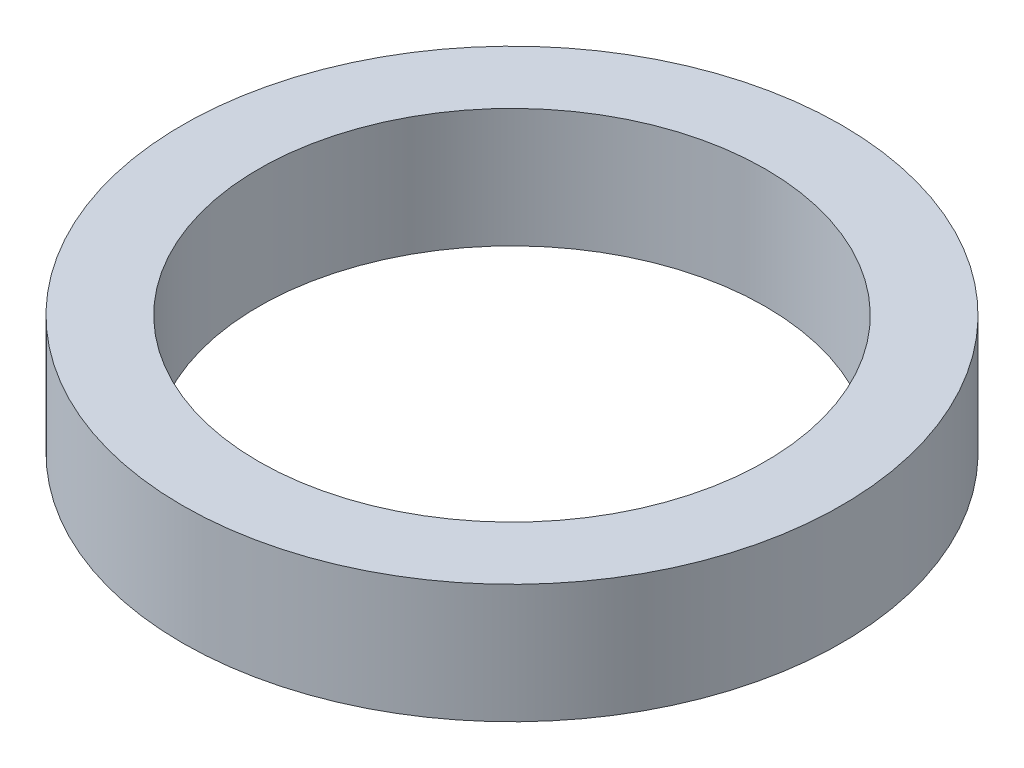
SolidWorks part; units mm, degrees
material "6061-T6 (SS)"
ref_plane "Front Plane" through (0, 0, 0) normal (0, 0, 1) x (1, 0, 0)
ref_plane "Top Plane" through (0, 0, 0) normal (0, 1, 0) x (1, 0, 0)
ref_plane "Right Plane" through (0, 0, 0) normal (1, 0, 0) x (0, 0, -1)
sketch "Sketch1" plane through (0, 0, 0) normal (0, 1, 0) x (1, 0, 0)
  circle A0 centre (0, 0) radius 3.3782
  circle A1 centre (0, 0) radius 4.3942
  dimension "D1" = 6.7564
  dimension "D2" = 1.016
extrude "Boss-Extrude1" add sketch "Sketch1" along normal blind 1.5875
